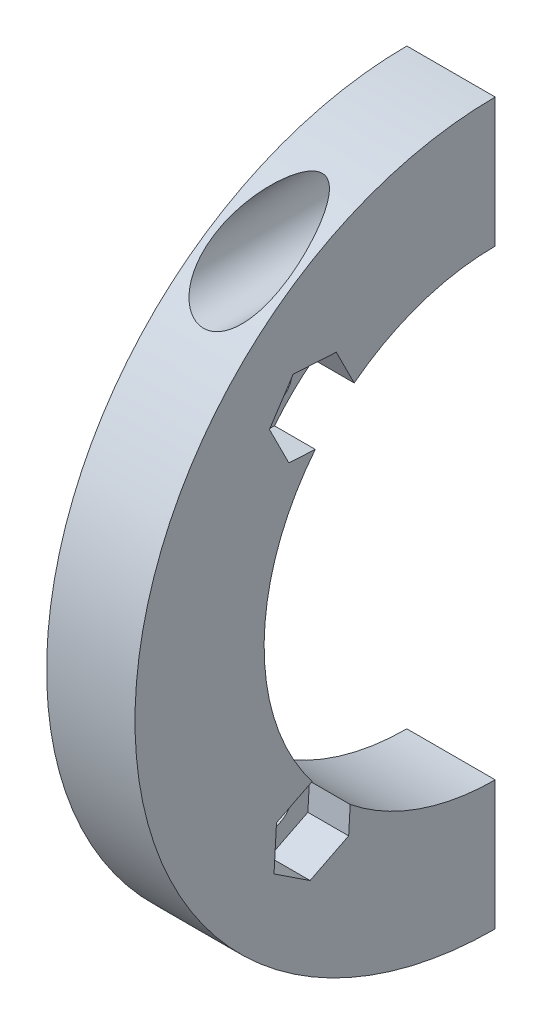
SolidWorks part; units mm, degrees
ref_plane "Front Plane" through (0, 0, 0) normal (0, 0, 1) x (1, 0, 0)
ref_plane "Top Plane" through (0, 0, 0) normal (0, 1, 0) x (1, 0, 0)
ref_plane "Right Plane" through (0, 0, 0) normal (1, 0, 0) x (0, 0, -1)
sketch "Sketch1" plane through (0, 0, 0) normal (1, 0, 0) x (0, 0, -1)
  line L0 (0, 49.9447) -> (0, -38.7058)
  line L1 (0, 0) -> (-13.435, 13.435)
  circle A0 centre (0, 0) radius 26.5
  circle A1 centre (0, 0) radius 17
  circle A2 centre (-13.435, 13.435) radius 1.5
  circle A3 centre (13.435, 13.435) radius 1.5
  circle A4 centre (13.435, -13.435) radius 1.5
  circle A5 centre (-13.435, -13.435) radius 1.5
  point P17 (0, 0)
  dimension "D1" = 53
  dimension "D2" = 34
  dimension "D5" = 3
  dimension "D3" = 45
  dimension "D4" = 19
  dimension "D6" = 4
extrude "Boss-Extrude1" add sketch "Sketch1" along normal blind 3.25 and the other way blind 3.25 contours A1 L0 A0 region at (0, 21.75, 0.5926)
sketch "Sketch3" plane through (0, 0, 0) normal (0, 0, -1) x (-1, 0, 0)
  line L1 (3.25, 17) -> (-3.25, 17) construction
  circle A0 centre (0, 22) radius 1.5
  dimension "D1" = 3
  dimension "D2" = 5
extrude "Cut-Extrude1" cut sketch "Sketch3" against normal blind 25.5
mirror "Mirror1" about plane through (0, 0, 0) normal (0, 1, 0) of "Cut-Extrude1"
ref_plane "Plane1" through (0, 0, 30) normal (0, 0, -1) x (-1, 0, 0)
sketch "Sketch4" plane through (0, 0, 30) normal (0, 0, -1) x (-1, 0, 0)
  circle A2 centre (0, 22) radius 2.75
  circle A3 centre (0, 22) radius 2.75
  dimension "D1" = 1.25
extrude "Cut-Extrude2" cut sketch "Sketch4" along normal blind 25
sketch "Sketch5" plane through (0, 0, 30) normal (0, 0, -1) x (-1, 0, 0)
  line L0 (-3.25, -17) -> (-3.25, -26.5) construction
  line L1 (2.75, -23.5877) -> (2.75, -20.4123)
  line L2 (2.75, -20.4123) -> (0, -18.8246)
  line L3 (0, -18.8246) -> (-2.75, -20.4123)
  line L4 (-2.75, -20.4123) -> (-2.75, -23.5877)
  line L5 (-2.75, -23.5877) -> (0, -25.1754)
  line L6 (0, -25.1754) -> (2.75, -23.5877)
  circle A1 centre (0, -22) radius 2.75 construction
  dimension "D1" = 5.5
  dimension "D2" = 0
extrude "Cut-Extrude3" cut sketch "Sketch5" along normal blind 25
sketch "Sketch6" plane through (3.25, 0, 0) normal (1, 0, 0) x (0, 0, -1)
  line L18 (-16.0883, -11.6904) -> (-16.2725, -14.8605)
  line L19 (-11.6904, 16.0883) -> (-14.8605, 16.2725)
  line L20 (-14.8605, 16.2725) -> (-16.6051, 13.6193)
  line L21 (-16.6051, 13.6193) -> (-15.1797, 10.7818)
  line L22 (-15.1797, 10.7818) -> (-12.0096, 10.5975)
  line L23 (-12.0096, 10.5975) -> (-10.265, 13.2508)
  line L24 (-10.265, 13.2508) -> (-11.6904, 16.0883)
  line L25 (-16.2725, -14.8605) -> (-13.6193, -16.6051)
  line L26 (-13.6193, -16.6051) -> (-10.7818, -15.1797)
  line L27 (-10.7818, -15.1797) -> (-10.5975, -12.0096)
  line L28 (-10.5975, -12.0096) -> (-13.2508, -10.265)
  line L29 (-13.2508, -10.265) -> (-16.0883, -11.6904)
  line L30 (11.6904, -16.0883) -> (14.8605, -16.2725)
  line L31 (14.8605, -16.2725) -> (16.6051, -13.6193)
  line L32 (16.6051, -13.6193) -> (15.1797, -10.7818)
  line L33 (15.1797, -10.7818) -> (12.0096, -10.5975)
  line L34 (12.0096, -10.5975) -> (10.265, -13.2508)
  line L35 (10.265, -13.2508) -> (11.6904, -16.0883)
  line L36 (16.0883, 11.6904) -> (16.2725, 14.8605)
  line L37 (16.2725, 14.8605) -> (13.6193, 16.6051)
  line L38 (13.6193, 16.6051) -> (10.7818, 15.1797)
  line L39 (10.7818, 15.1797) -> (10.5975, 12.0096)
  line L40 (10.5975, 12.0096) -> (13.2508, 10.265)
  line L41 (13.2508, 10.265) -> (16.0883, 11.6904)
  circle A1 centre (-13.435, 13.435) radius 2.75 construction
  point P32 (0, 0)
  dimension "D1" = 4
  dimension "D3" = 5.5
extrude "Cut-Extrude4" cut sketch "Sketch6" against normal blind 3
